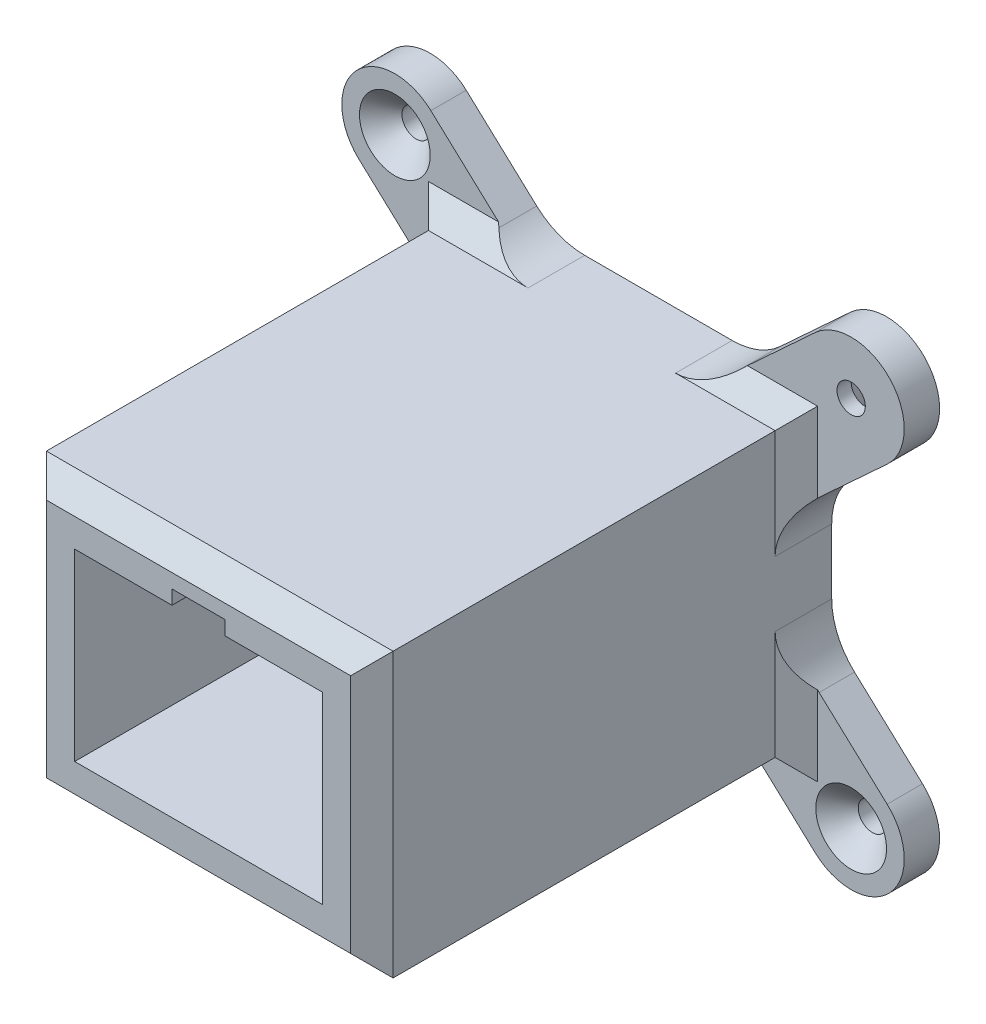
SolidWorks part; units mm, degrees
ref_plane "Top Plane" through (0, 0, 0) normal (0, 0, 1) x (1, 0, 0)
ref_plane "Right Plane" through (0, 0, 0) normal (0, 1, 0) x (1, 0, 0)
ref_plane "Front Plane" through (0, 0, 0) normal (1, 0, 0) x (0, 0, -1)
sketch "Sketch1" plane through (0, 0, 0) normal (0, 0, 1) x (1, 0, 0)
  line L0 (-24.5, -20) -> (24.5, 20) construction
  line L1 (-17.5, -13) -> (17.5, -13)
  line L2 (-17.5, -13) -> (-17.5, 13)
  line L3 (-17.5, 13) -> (-3.75, 13)
  line L4 (17.5, -13) -> (17.5, 13)
  line L5 (-24.5, -20) -> (24.5, -20)
  line L6 (-24.5, -20) -> (-24.5, 20)
  line L7 (-24.5, 20) -> (24.5, 20)
  line L8 (24.5, -20) -> (24.5, 20)
  line L9 (-17.5, 13) -> (17.5, -13) construction
  line L10 (17.5, -20) -> (17.5, -13) construction
  line L11 (17.5, -13) -> (24.5, -13) construction
  line L12 (3.75, 13) -> (17.5, 13)
  line L14 (-3.75, 13) -> (-3.75, 15)
  line L15 (-3.75, 15) -> (3.75, 15)
  line L16 (3.75, 13) -> (3.75, 15)
  point P9 (0, 0)
  dimension "D1" = 35
  dimension "D2" = 26
  dimension "D3" = 7
  dimension "D4" = 7.5
  dimension "D5" = 2
extrude "Boss-Extrude1" add sketch "Sketch1" along normal blind 60
ref_axis "Axis1" through (0, 0, -2.5) along (0, 0, 1)
sketch "Sketch2" plane through (0, 0, 0) normal (0, 0, 1) x (1, 0, 0)
  line L1 (-24.5, 20) -> (24.5, 20)
  line L2 (-24.5, 20) -> (-24.5, -20)
  line L3 (-24.5, -20) -> (24.5, -20)
  line L4 (24.5, 20) -> (24.5, -20)
extrude "Boss-Extrude2" add sketch "Sketch2" against normal blind 5
sketch "Sketch3" plane through (0, 0, 0) normal (0, 0, 1) x (1, 0, 0)
  line L0 (4, -4) -> (-4, 4) construction
  line L1 (4, 4) -> (-4, 4)
  line L2 (4, 4) -> (4, -4)
  line L3 (4, -4) -> (-4, -4)
  line L4 (-4, 4) -> (-4, -4)
  line L5 (12, 0.25) -> (-12, 0.25) construction
  line L7 (0, 0) -> (0, 0.25) construction
  circle A0 centre (12, 0.25) radius 3.75
  circle A1 centre (-12, 0.25) radius 3.75
  circle A2 centre (12, 0.25) radius 3.75 construction
  point P4 (0, 0)
  point P5 (0, 0)
  dimension "D1" = 8
extrude "Cut-Extrude1" cut sketch "Sketch3" against normal blind 4
sketch "Sketch4" plane through (0, 0, -5) normal (0, 0, -1) x (-1, 0, 0)
  line L0 (27.1614, 31.8365) -> (14.3296, 20)
  line L1 (-24.5, 20) -> (24.5, 20) construction
  line L2 (14.3296, 20) -> (24.5, 8.9744)
  line L3 (24.5, 20) -> (24.5, -20) construction
  line L4 (24.5, 8.9744) -> (37.3318, 20.811)
  line L5 (0, 0) -> (32.2466, 26.3238) construction
  circle A0 centre (32.2466, 26.3238) radius 2
  arc A1 (37.3318, 20.811) -> (27.1614, 31.8365) centre (32.2466, 26.3238) ccw
  dimension "D1" = 15
  dimension "D2" = 4
  dimension "D3" = 10
extrude "Boss-Extrude3" add sketch "Sketch4" against normal blind 5
mirror "Mirror1" about plane through (0, 0, 0) normal (0, 1, 0) of "Boss-Extrude3"
mirror "Mirror2" about plane through (0, 0, 0) normal (1, 0, 0) of "Mirror1"
chamfer "Chamfer2" distance 3 angle 45 12 edges at (-19.4148, -20, 0) (-24.5, -14.4872, 0) (-24.5, 14.4872, 0) (-19.4148, 20, 0) (19.4148, 20, 0) (24.5, 14.4872, 0) (24.5, -14.4872, 0) (19.4148, -20, 0) (34.2466, -26.3238, 0) (34.2466, 26.3238, -5) (-34.2466, -26.3238, 0) (-34.2466, 26.3238, 0)
fillet "Fillet1" radius 10 8 edges at (-14.3296, -20, -1) (14.3296, -20, -1) (-24.5, 8.9744, -1) (-24.5, -8.9744, -1) (-14.3296, 20, -1) (14.3296, 20, -1) (24.5, 8.9744, -1) (24.5, -8.9744, -1)
chamfer "Chamfer3" distance 3 angle 45 4 edges at (0, 20, 60) (-24.5, 0, 60) (0, -20, 60) (24.5, 0, 60)
